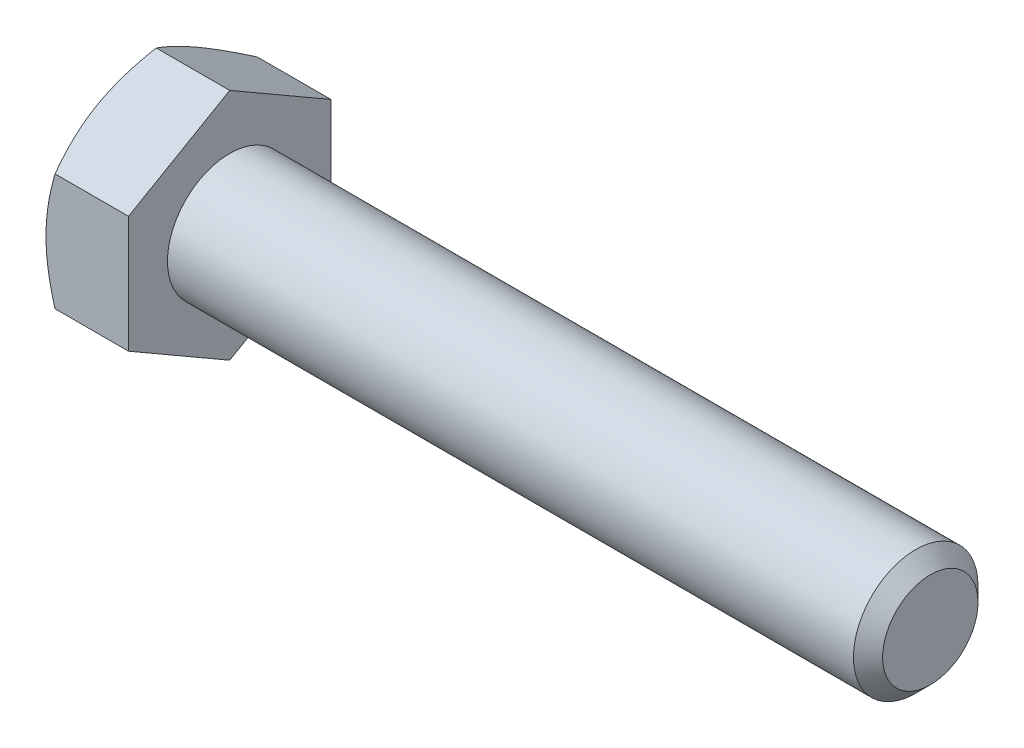
SolidWorks part; units mm, degrees
material "Alloy Steel"
ref_plane "Front Plane" through (0, 0, 0) normal (0, 0, 1) x (1, 0, 0)
ref_plane "Top Plane" through (0, 0, 0) normal (0, 1, 0) x (1, 0, 0)
ref_plane "Right Plane" through (0, 0, 0) normal (1, 0, 0) x (0, 0, -1)
sketch "Sketch1" plane through (0, 0, 0) normal (0, 0, 1) x (1, 0, 0)
  line L0 (-25.15, 0) -> (25.15, 0) construction
  line L1 (-19.85, 6.5) -> (-19.85, -6.5) construction
  line L2 (-25.15, 6.5) -> (-25.15, -6.5) construction
  line L3 (25.15, 4) -> (25.15, -4) construction
  point P8 (20.775, -4)
  dimension "Thread Dia" = 8
  dimension "Hex" = 13
  dimension "Head Ht" = 5.3
  dimension "Length" = 45
  dimension "D1" = 4.375
ref_plane "Plane2" through (25.15, 0, 0) normal (1, 0, 0) x (0, 0, -1)
sketch "Sketch2" plane through (25.15, 0, 0) normal (1, 0, 0) x (0, 0, -1)
  circle A0 centre (0, 0) radius 4
extrude "Boss-Extrude1" add sketch "Sketch2" against normal up to vertex (45 mm away) up to point (-19.85, -6.5, 0)
sketch "Sketch4" plane through (25.15, 0, 0) normal (1, 0, 0) x (0, 0, -1)
  circle A1 centre (0, 0) radius 4
  circle A2 centre (0, 0) radius 4
  dimension "D1" = 0
curve "Helix/Spiral1" [suppressed] parameters "Pitch"=1.25
chamfer "Chamfer1" distance 0.9375 angle 45 1 edges at (25.15, 0, -4)
sketch "Sketch5" plane through (0, 0, 0) normal (0, 0, 1) x (1, 0, 0)
  line L0 (25.15, 4) -> (25.6188, 3.1881)
  line L1 (25.6188, 3.1881) -> (25.775, 3.1881)
  line L2 (25.775, 3.1881) -> (26.2438, 4)
  line L3 (25.15, 4) -> (26.2438, 4)
  line L4 (25.6969, 3.1881) -> (25.6969, 4) construction
  line L5 (25.3844, 3.5941) -> (26.0094, 3.5941) construction
  line L6 (25.15, -4) -> (25.15, 4) construction
  dimension "D1" = 60
  dimension "D2" = 0.1562
  dimension "D3" = 0.625
sweep "Cut-Sweep1" [suppressed] cut profiles "Sketch5" path "Helix/Spiral1"
sketch "Sketch3" plane through (-19.85, 0, 0) normal (-1, 0, 0) x (0, 0, 1)
  line L0 (0, 6.5) -> (0, -6.5) construction
  line L1 (-6.5, -3.7528) -> (0, -7.5056)
  line L2 (0, -7.5056) -> (6.5, -3.7528)
  line L3 (6.5, -3.7528) -> (6.5, 3.7528)
  line L4 (6.5, 3.7528) -> (0, 7.5056)
  line L5 (0, 7.5056) -> (-6.5, 3.7528)
  line L6 (-6.5, 3.7528) -> (-6.5, -3.7528)
  circle A0 centre (0, 0) radius 6.5 construction
extrude "Boss-Extrude2" add sketch "Sketch3" along normal up to vertex (5.3 mm away) up to point (-25.15, -6.5, 0)
sketch "Sketch6" plane through (-25.15, 0, 0) normal (-1, 0, 0) x (0, 0, 1)
  circle A0 centre (0, 0) radius 6.5 construction
  circle A1 centre (0, 0) radius 6.5
extrude "Cut-Extrude1" cut sketch "Sketch6" against normal through all draft 60 flip side to cut
sketch "Sketch9" plane through (0, 0, 0) normal (0, 0, 1) x (1, 0, 0)
  line L0 (-19.85, 4) -> (-19.85, 0)
  line L1 (-19.85, 0) -> (-24.85, 0)
  line L2 (-24.85, 0) -> (-28.85, 4)
  line L3 (-28.85, 4) -> (-19.85, 4)
  line L4 (-25.15, 0) -> (25.15, 0) construction
  line L5 (-19.85, 6.5) -> (-19.85, -6.5) construction
  line L6 (25.15, 4) -> (25.15, -4) construction
  dimension "D1" = 45
  dimension "MinThreadLg" = 54
revolve "Revolve1" [suppressed] add sketch "Sketch9" angle 360 about L1
equation "\"D2@Sketch5\" = \"Pitch@Helix/Spiral1\"*.125"
equation "\"D3@Sketch5\" = \"Pitch@Helix/Spiral1\"*.50"
equation "\"D3@Helix/Spiral1\" = \"Length@Sketch1\"+\"Pitch@Helix/Spiral1\""
equation "\"D1@Chamfer1\" = \"Pitch@Helix/Spiral1\"*.750"
equation "\"D1@Sketch1\" = \"Pitch@Helix/Spiral1\"*3.50"
